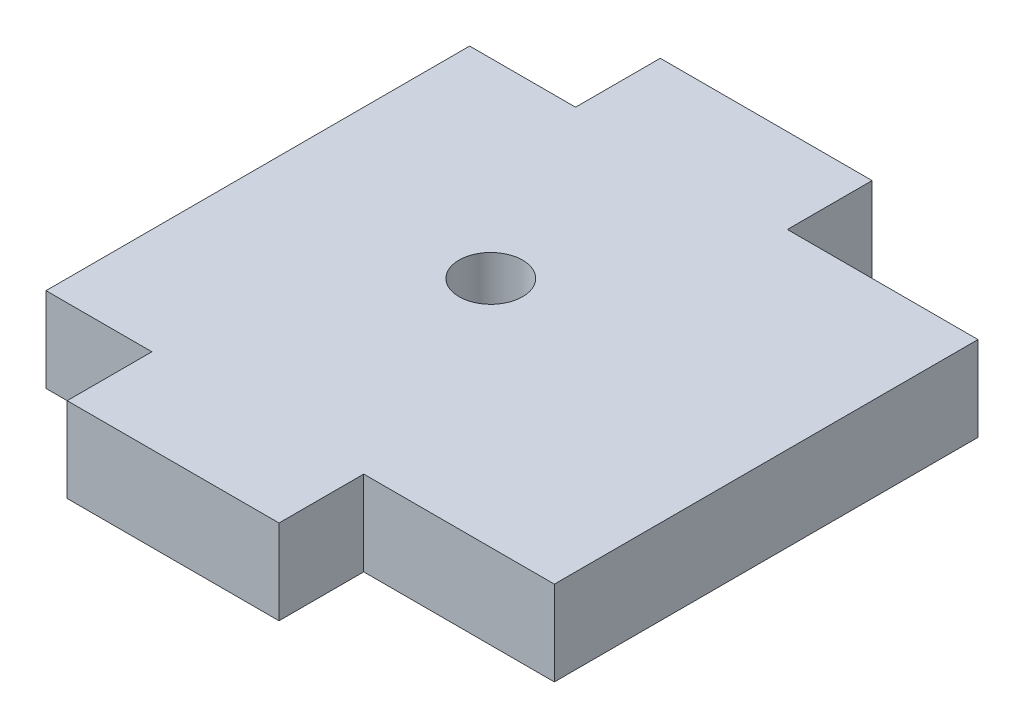
SolidWorks part; units mm, degrees
ref_plane "Front Plane" through (0, 0, 0) normal (0, 0, 1) x (1, 0, 0)
ref_plane "Top Plane" through (0, 0, 0) normal (0, 1, 0) x (1, 0, 0)
ref_plane "Right Plane" through (0, 0, 0) normal (1, 0, 0) x (0, 0, -1)
sketch "Sketch1" plane through (0, 0, 0) normal (0, 1, 0) x (1, 0, 0)
  line L0 (15, 20) -> (24, 20)
  line L5 (0, 0) -> (5, 0)
  line L6 (0, 0) -> (0, 20)
  line L7 (0, 20) -> (5, 20)
  line L8 (24, 0) -> (24, 20)
  line L18 (5, 20) -> (5, 24)
  line L19 (5, 24) -> (15, 24)
  line L20 (15, 20) -> (15, 24)
  line L22 (5, 0) -> (5, -4)
  line L23 (5, -4) -> (15, -4)
  line L24 (15, 0) -> (15, -4)
  line L25 (15, 0) -> (24, 0)
  line L26 (10, 24) -> (10, -2) construction
  line L27 (0, 10) -> (24, 10) construction
  circle A0 centre (10, 11) radius 1.5
  dimension "D1" = 4
  dimension "D2" = 10
  dimension "D3" = 24
  dimension "D4" = 20
  dimension "D5" = 5
  dimension "D6" = 5
  dimension "D7" = 10
  dimension "D8" = 4
extrude "Boss-Extrude2" add sketch "Sketch1" along normal blind 4
